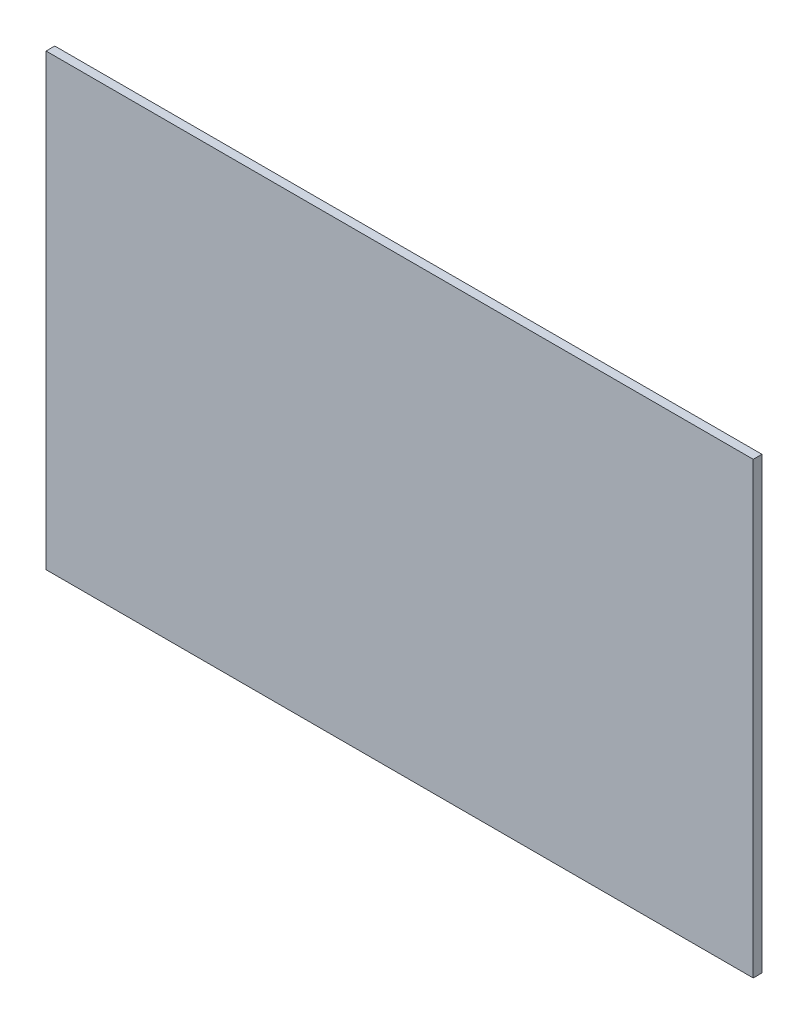
SolidWorks part; units mm, degrees
ref_plane "Front Plane" through (0, 0, 0) normal (0, 0, 1) x (1, 0, 0)
ref_plane "Top Plane" through (0, 0, 0) normal (0, 1, 0) x (1, 0, 0)
ref_plane "Right Plane" through (0, 0, 0) normal (1, 0, 0) x (0, 0, -1)
sketch "Sketch1" plane through (0, 0, 0) normal (0, 0, 1) x (1, 0, 0)
  line L1 (0, 0) -> (2440, 0)
  line L2 (0, 0) -> (0, 1550)
  line L3 (0, 1550) -> (2440, 1550)
  line L4 (2440, 0) -> (2440, 1550)
  dimension "D1" = 2440
  dimension "D2" = 1550
extrude "Boss-Extrude1" add sketch "Sketch1" along normal blind 30
